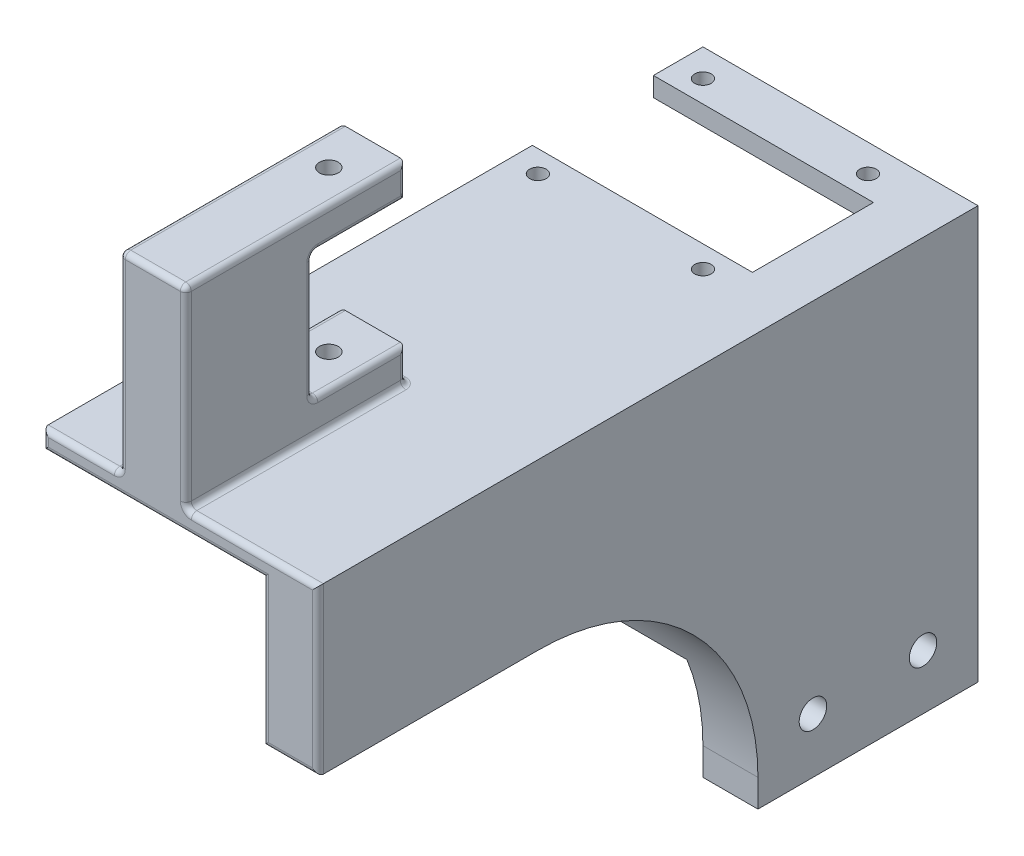
SolidWorks part; units mm, degrees
ref_plane "Front Plane" through (0, 0, 0) normal (0, 0, 1) x (1, 0, 0)
ref_plane "Top Plane" through (0, 0, 0) normal (0, 1, 0) x (1, 0, 0)
ref_plane "Right Plane" through (0, 0, 0) normal (1, 0, 0) x (0, 0, -1)
sketch "Sketch1" plane through (0, 0, 0) normal (1, 0, 0) x (0, 0, -1)
  line L0 (0, 27.5) -> (0, -27.5) construction
  line L5 (-20, 55) -> (20, 55)
  line L6 (-20, 55) -> (-20, 0)
  line L7 (-20, 0) -> (20, 0)
  line L8 (20, 55) -> (20, 0)
  line L9 (-20, 55) -> (20, 0) construction
  line L10 (-20, 0) -> (20, 55) construction
  line L11 (27.5, 0) -> (-27.5, 0) construction
  line L13 (-20, -20) -> (20, -20)
  line L14 (-20, -20) -> (-20, 0)
  line L15 (-20, 0) -> (20, 0)
  line L16 (20, -20) -> (20, 0)
  line L17 (-20, -20) -> (20, 0) construction
  line L18 (-20, 0) -> (20, -20) construction
  line L19 (10, -15) -> (-10, -15) construction
  line L20 (10, -15) -> (10, -5) construction
  line L21 (10, -5) -> (-10, -5) construction
  line L22 (-10, -15) -> (-10, -5) construction
  line L23 (10, -15) -> (-10, -5) construction
  line L24 (10, -5) -> (-10, -15) construction
  circle A0 centre (-10, -10) radius 2.5
  circle A1 centre (10, -10) radius 2.5
  point P1 (0, 27.5)
  point P10 (0, -10)
  point P11 (0, -10)
  dimension "D5" = 5
  dimension "D1" = 55
  dimension "D2" = 40
  dimension "D3" = 20
  dimension "D4" = 20
extrude "Boss-Extrude1" add sketch "Sketch1" along normal blind 10 contours L8 L5 L6 L7 | L13 L16 L7 L14 A1 A0 region at (0, 27.5, 0) region at (0, -10, 0)
sketch "Sketch3" plane through (0, 0, 0) normal (-1, 0, 0) x (0, 0, 1)
  line L0 (20, 55) -> (20, -20) construction
  line L1 (-20, 10) -> (20, 10)
  line L2 (-20, 10) -> (-20, 0)
  line L3 (-20, 0) -> (20, 0)
  line L4 (20, 10) -> (20, 0)
  line L5 (-20, 10) -> (20, 0) construction
  line L6 (-20, 0) -> (20, 10) construction
  dimension "D1" = 10
extrude "Boss-Extrude2" add sketch "Sketch3" along normal blind 40
sketch "Sketch4" plane through (0, 0, 0) normal (-1, 0, 0) x (0, 0, 1)
  line L13 (-20, 55) -> (-11, 55)
  line L14 (-20, 55) -> (-20, 51.5)
  line L15 (-20, 51.5) -> (-11, 51.5)
  line L16 (-11, 55) -> (-11, 51.5)
  dimension "D1" = 9
  dimension "D2" = 3.5
extrude "Boss-Extrude3" add sketch "Sketch4" along normal blind 40
sketch "Sketch5" plane through (0, 55, 0) normal (0, 1, 0) x (1, 0, 0)
  line L1 (-40, 20) -> (-35, 20) construction
  line L2 (-40, 20) -> (-40, 15) construction
  line L3 (-40, 15) -> (-35, 15) construction
  line L4 (-35, 20) -> (-35, 15) construction
  line L5 (10, 20) -> (-40, 20) construction
  line L7 (0, 20) -> (-5, 20) construction
  line L8 (0, 20) -> (0, 15) construction
  line L9 (0, 15) -> (-5, 15) construction
  line L10 (-5, 20) -> (-5, 15) construction
  circle A0 centre (-35, 15) radius 1.5
  circle A1 centre (-5, 15) radius 1.5
  dimension "D3" = 3
  dimension "D7" = 3
  dimension "D1" = 5
  dimension "D2" = 5
  dimension "D4" = 5
  dimension "D5" = 5
  dimension "D6" = 30
extrude "Cut-Extrude1" cut sketch "Sketch5" against normal up to next
mirror "Mirror2" about plane through (0, 0, 0) normal (0, 0, 1) of "Cut-Extrude1", "Boss-Extrude3"
sketch "Sketch7" plane through (0, 0, 20) normal (0, 0, 1) x (1, 0, 0)
  line L0 (0, -44) -> (0, 44) construction
  line L1 (-40, 55) -> (0, 55)
  line L2 (-40, 55) -> (-40, 51.5)
  line L3 (-40, 51.5) -> (0, 51.5)
  line L4 (0, 55) -> (0, 51.5)
  line L5 (-20, 51.5) -> (-20, 55) construction
  line L6 (-40, 53.25) -> (0, 53.25) construction
  line L7 (-40, 51.5) -> (0, 51.5) construction
  line L8 (10, 55) -> (10, -20) construction
  line L9 (0, 55) -> (10, 55)
  line L10 (0, 55) -> (0, 25)
  line L11 (0, 25) -> (10, 25)
  line L12 (10, 55) -> (10, 25)
  line L13 (5, 25) -> (5, 55) construction
  line L14 (0, 40) -> (10, 40) construction
  point P199 (5, 40)
  point P296 (-20, 53.25)
  line M2 (10, 55) -> (-40, 55)
  line M3 (-40, 55) -> (-40, 51.5)
  line M4 (-40, 51.5) -> (0, 51.5)
  line M5 (0, 51.5) -> (0, 10)
  line M11 (10, -20) -> (10, 55)
  dimension "D1" = 30
extrude "Boss-Extrude4" add sketch "Sketch7" along normal blind 80 contours L4 M2 M3 M4 | L11 L4 M5 M11 M2 region at (-20, 53.25, 20) region at (5, 40, 20)
sketch "Sketch8" plane through (0, 55, 0) normal (0, 1, 0) x (1, 0, 0)
  line L0 (10, -100) -> (-40, -100) construction
  line L1 (-26, -100) -> (-14, -100)
  line L2 (-26, -100) -> (-26, -60)
  line L3 (-26, -60) -> (-14, -60)
  line L4 (-14, -100) -> (-14, -60)
  line L5 (-20, -60) -> (-20, -100) construction
  line L6 (-26, -80) -> (-14, -80) construction
  line L7 (-40, -11) -> (-40, -100) construction
  line L8 (0, -60.5) -> (0, 60.5) construction
  point P100 (-20, -80)
  dimension "D1" = 12
  dimension "D2" = 40
extrude "Boss-Extrude5" add sketch "Sketch8" along normal blind 35
sketch "Sketch9" plane through (0, 0, 60) normal (0, 0, -1) x (-1, 0, 0)
  line L0 (14, 90) -> (14, 55) construction
  line L1 (14, 84) -> (26, 84)
  line L2 (14, 84) -> (14, 61)
  line L3 (14, 61) -> (26, 61)
  line L4 (26, 84) -> (26, 61)
  line L5 (20, 61) -> (20, 84) construction
  line L6 (14, 72.5) -> (26, 72.5) construction
  line L7 (26, 90) -> (26, 55) construction
  line L8 (14, 90) -> (26, 90) construction
  line L9 (-10, 55) -> (40, 55) construction
  point P172 (20, 72.5)
  dimension "D1" = 6
  dimension "D2" = 6
extrude "Cut-Extrude2" cut sketch "Sketch9" against normal blind 17
sketch "Sketch10" plane through (0, 90, 0) normal (0, 1, 0) x (1, 0, 0)
  line L0 (-20, -1038.2105) -> (-20, 48961.7895) construction
  line L1 (-26, -60) -> (-26, -100) construction
  line L2 (-14, -100) -> (-14, -60) construction
  line L4 (-14, -60) -> (-26, -60) construction
  circle A0 centre (-20, -68) radius 1.7
  dimension "D1" = 3.4
  dimension "D2" = 8
extrude "Cut-Extrude3" cut sketch "Sketch10" against normal up to surface (38.5 mm away) and the other way through all contours A0 up to face at (-35, 51.5, 13.5)
fillet "Fillet1" radius 1 27 edges at (-20, 55, 60) (-40, 53.25, 100) (-33, 55, 100) (-20, 90, 100) (-2, 55, 100) (10, 40, 100) (5, 25, 100) (0, 38.25, 100) (-20, 51.5, 100) (-14, 61, 68.5) (-14, 58, 60) (-14, 55, 80) (-14, 72.5, 100) (-14, 90, 80) (-14, 87, 60) (-14, 84, 68.5) (-26, 90, 80) (-26, 72.5, 100) (-26, 55, 80) (-26, 58, 60) (-26, 61, 68.5) (-26, 84, 68.5) (-26, 87, 60) (-20, 84, 77) (-26, 72.5, 77) (-20, 61, 77) (-14, 72.5, 77)
fillet "Fillet2" radius 40 1 edges at (5, 25, 20)
